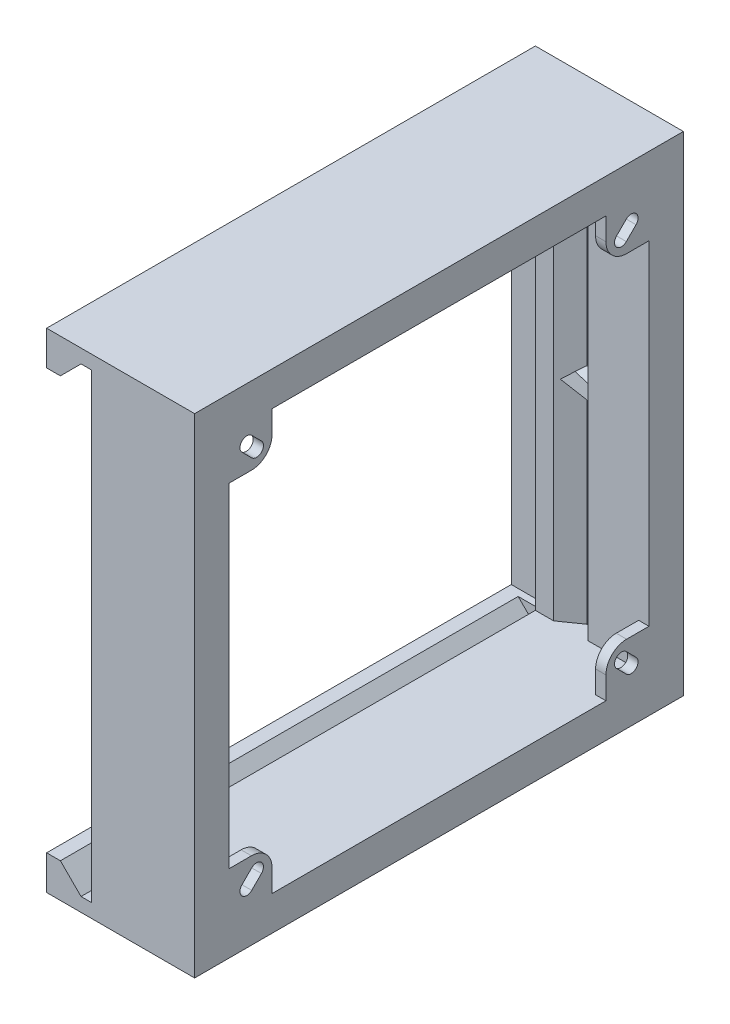
SolidWorks part; units mm, degrees
ref_plane "Front Plane" through (0, 0, 0) normal (1, 0, 0) x (0, 1, 0)
ref_plane "Top Plane" through (0, 0, 0) normal (0, 0, 1) x (0, 1, 0)
ref_plane "Right Plane" through (0, 0, 0) normal (0, 1, 0) x (-1, 0, 0)
sketch "Sketch2" plane through (0, 0, 0) normal (1, 0, 0) x (0, 1, 0)
  line L0 (-71, -71) -> (-71, 71)
  line L1 (-61, -61) -> (61, -61)
  line L2 (-61, -61) -> (-61, 61)
  line L3 (-61, 61) -> (61, 61)
  line L4 (61, -61) -> (61, 61)
  line L5 (-61, -61) -> (61, 61) construction
  line L6 (-61, 61) -> (61, -61) construction
  line L7 (-71, 71) -> (71, 71)
  line L8 (71, -71) -> (71, 71)
  line L9 (-71, -71) -> (71, -71)
  line L10 (-48.5, 61) -> (-48.5, 54.5)
  line L11 (-54.5, 48.5) -> (-61, 48.5)
  line L12 (-53, 53) -> (-55.8284, 55.8284) construction
  line L13 (-54.4142, 51.5858) -> (-57.2426, 54.4142)
  line L14 (-51.5858, 54.4142) -> (-54.4142, 57.2426)
  line L15 (48.5, 54.5) -> (48.5, 61)
  line L16 (61, 48.5) -> (54.5, 48.5)
  line L17 (53, 53) -> (55.8284, 55.8284) construction
  line L18 (51.5858, 54.4142) -> (54.4142, 57.2426)
  line L19 (54.4142, 51.5858) -> (57.2426, 54.4142)
  line L20 (54.5, -48.5) -> (61, -48.5)
  line L21 (48.5, -61) -> (48.5, -54.5)
  line L22 (53, -53) -> (55.8284, -55.8284) construction
  line L23 (54.4142, -51.5858) -> (57.2426, -54.4142)
  line L24 (51.5858, -54.4142) -> (54.4142, -57.2426)
  line L25 (-48.5, -54.5) -> (-48.5, -61)
  line L26 (-61, -48.5) -> (-54.5, -48.5)
  line L27 (-53, -53) -> (-55.8284, -55.8284) construction
  line L28 (-51.5858, -54.4142) -> (-54.4142, -57.2426)
  line L29 (-54.4142, -51.5858) -> (-57.2426, -54.4142)
  arc A0 (-48.5, 54.5) -> (-54.5, 48.5) centre (-54.5, 54.5) cw
  arc A2 (-54.4142, 51.5858) -> (-51.5858, 54.4142) centre (-53, 53) ccw
  arc A3 (-54.4142, 57.2426) -> (-57.2426, 54.4142) centre (-55.8284, 55.8284) ccw
  arc A4 (54.5, 48.5) -> (48.5, 54.5) centre (54.5, 54.5) cw
  arc A5 (51.5858, 54.4142) -> (54.4142, 51.5858) centre (53, 53) ccw
  arc A6 (57.2426, 54.4142) -> (54.4142, 57.2426) centre (55.8284, 55.8284) ccw
  arc A7 (48.5, -54.5) -> (54.5, -48.5) centre (54.5, -54.5) cw
  arc A8 (54.4142, -51.5858) -> (51.5858, -54.4142) centre (53, -53) ccw
  arc A9 (54.4142, -57.2426) -> (57.2426, -54.4142) centre (55.8284, -55.8284) ccw
  arc A10 (-54.5, -48.5) -> (-48.5, -54.5) centre (-54.5, -54.5) cw
  arc A11 (-51.5858, -54.4142) -> (-54.4142, -51.5858) centre (-53, -53) ccw
  arc A12 (-57.2426, -54.4142) -> (-54.4142, -57.2426) centre (-55.8284, -55.8284) ccw
  point P0 (0, 0)
  point P14 (-50.2574, 50.2574)
  point P18 (-54.4142, 54.4142)
  point P33 (54.4142, 54.4142)
  point P45 (54.4142, -54.4142)
  point P57 (-54.4142, -54.4142)
  point P62 (0, 0)
  dimension "D4" = 6
  dimension "D6" = 2
  dimension "D8" = 4
  dimension "D1" = 122
  dimension "D2" = 122
  dimension "D5" = 12.5
  dimension "D7" = 8
  dimension "D3" = 10
  dimension "D9" = 4
extrude "Boss-Extrude1" add sketch "Sketch2" along normal blind 3 contours A0 L10 L3 L2 L11 A3 L14 A2 L13 | L0 L9 L8 L7 L4 L1 L2 L3 | A4 L16 L4 L3 L15 A6 L19 A5 L18 | A7 L21 L1 L4 L20 A9 L24 A8 L23 | A10 L26 L2 L1 L25 A12 L29 A11 L28 region at (0, -68.9918, 0) region at (0, -60.8232, -54.75) region at (0, 48.6768, -57.75) region at (0, -60.8232, 54.75) region at (0, 57.75, 48.6768)
extrude "Boss-Extrude2" add sketch "Sketch2<4>" against normal blind 30 contours L0 L9 L8 L7 L4 L1 L2 L3 region at (0, -68.9918, 0)
sketch "Sketch2<4>" plane through (0, 0, 0) normal (1, 0, 0) x (0, 1, 0) same geometry as "Sketch2"
sketch "Sketch3" plane through (-30, 0, 0) normal (-1, 0, 0) x (0, -1, 0)
  line L0 (-61, -61) -> (-61, 61)
  line L1 (-61, 61) -> (-61, 71)
  line L2 (71, 71) -> (-71, 71) construction
  line L3 (-61, 71) -> (-71, 71)
  line L4 (71, -71) -> (71, 71)
  line L5 (71, 71) -> (-71, 71)
  line L6 (-71, 71) -> (-71, -71)
  line L7 (-71, -71) -> (71, -71)
  line L8 (71, -71) -> (71, 71)
  line L10 (-71, 71) -> (-71, -71)
  line L11 (-71, -71) -> (71, -71)
  line L12 (71, 71) -> (61, 71)
  line L13 (61, 71) -> (61, 61)
  line L14 (61, 61) -> (61, -61)
  line L15 (61, -61) -> (-61, -61)
  dimension "D1" = 0
extrude "Boss-Extrude3" add sketch "Sketch3" along normal blind 10
sketch "Sketch6" plane through (0, 0, -61) normal (0, 0, 1) x (1, 0, 0)
  line L0 (-30, 61) -> (-30, 67)
  line L1 (-30, 67) -> (-36, 61)
  line L2 (-36, 61) -> (-30, 61)
  line L6 (-40, 61) -> (0, 61) construction
  line L7 (-30, -61) -> (-30, 61) construction
  line L8 (55, 0) -> (-55, 0) construction
  line L9 (-30, -67) -> (-36, -61)
  line L10 (-30, -61) -> (-30, -67)
  line L11 (-36, -61) -> (-30, -61)
  dimension "D1" = 45
  dimension "D2" = 6
extrude "Cut-Extrude3" cut sketch "Sketch6" along normal up to surface (132 mm away) from offset 1 up to face at (-26.75, 0, 71) offset against normal yes
sketch "Sketch5" plane through (-40, 0, 0) normal (-1, 0, 0) x (0, -1, 0)
  line L0 (-61, -61) -> (61, -61)
  line L1 (61, -61) -> (61, -64)
  line L2 (61, -64) -> (-61, -64)
  line L3 (-61, -64) -> (-61, -61)
  dimension "D1" = 3
extrude "Cut-Extrude2" cut sketch "Sketch5" against normal up to surface (10 mm away) up to face at (-30, 0, -10.6)
sketch "Sketch9" plane through (0, -71, 0) normal (0, -1, 0) x (1, 0, 0)
  line L1 (3, 71) -> (-40, 71) construction
  line L3 (-30, 68) -> (-27, 71)
  line L4 (-30, 71) -> (-30, -62) construction
  line L5 (-27, 71) -> (-30, 71)
  line L6 (-30, 71) -> (-30, 68)
  dimension "D1" = 45
  dimension "D2" = 3
extrude "Cut-Extrude4" cut sketch "Sketch9" against normal up to vertex (138 mm away) and the other way up to vertex (-4 mm away) from surface up to point (-30, 67, 71) other way up to point (-30, -67, 71) starting at plane "Right Plane"
sketch "Sketch11" plane through (0, 71, 0) normal (0, 1, 0) x (-1, 0, 0)
  line L0 (14.7126, -65) -> (19, -65)
  line L1 (19, -65) -> (24.7126, -61)
  line L2 (24.7126, -61) -> (14.7126, -61)
  line L3 (14.7126, -61) -> (14.7126, -65)
  line L4 (-3, -71) -> (40, -71) construction
  line L5 (-3, -71) -> (-3, 71) construction
  point P2 (0, 0)
  point P9 (0, 0)
  point P10 (29.7902, -65)
  dimension "D1" = 10
  dimension "D2" = 4
  dimension "D3" = 35
  dimension "D4" = 6
  dimension "D5" = 22
extrude "Cut-Extrude5" cut sketch "Sketch11" against normal up to surface (132 mm away) and the other way up to surface (-10 mm away) from surface up to face at (-6.75, -61, 0) other way up to face at (-35.3333, 61, -18.3333) starting at plane "Right Plane"
sketch "Sketch13" plane through (-40, 0, 0) normal (-1, 0, 0) x (0, -1, 0)
  line L0 (0, -64) -> (0, -66) construction
  line L1 (-61, -64) -> (61, -64) construction
  line L2 (0, -66) -> (-5, -68.3553)
  line L3 (-5, -68.3553) -> (-2, -71)
  line L4 (-71, -71) -> (71, -71) construction
  line L5 (-2, -71) -> (2, -71)
  line L6 (2, -71) -> (5, -68.3553)
  line L7 (5, -68.3553) -> (0, -66)
  line L8 (-5, -68.3553) -> (5, -68.3553) construction
  point P5 (0, -71)
  point P12 (0, -68.3553)
  point P13 (-5, -69.0979)
  point P14 (-5, -68.3553)
  dimension "D1" = 10
  dimension "D2" = 2
  dimension "D3" = 4
extrude "Cut-Extrude6" cut sketch "Sketch13" against normal up to surface (25.2874 mm away) up to face at (-14.7126, 0, -63)
sketch "Sketch14" plane through (0, 0, -65) normal (0, 0, 1) x (1, 0, 0)
  line L0 (-18.5699, -5) -> (-14.7126, -5)
  line L2 (-14.7126, -5) -> (-14.7126, 5)
  line L3 (-18.033, 5) -> (-14.7126, 5)
  line L6 (-14.7126, -61) -> (-14.7126, 61) construction
  line L9 (3, -48.5) -> (3, 48.5) construction
  line L10 (-18.033, 5) -> (-23.5699, 0)
  line L11 (-23.5699, 0) -> (-18.5699, -5)
  point P1 (-16.3728, 0)
  point P7 (-16.4903, -1.5353)
  point P11 (3, 0)
  point P13 (0, 0)
  point P15 (-23.5306, 0)
  point P16 (-17.9938, 5.8824)
  point P17 (0, 0)
  point P19 (0, 0)
  point P20 (-14.7126, 0)
  line M5 (-14.7126, -61) -> (-14.7126, 61)
  line M7 (-19, 61) -> (-19, -61)
  dimension "D1" = 10
  dimension "D2" = 45
extrude "Cut-Extrude7" cut sketch "Sketch14" against normal up to vertex (3.3553 mm away) from surface contours L11 L0 L3 L10 M7 M5 | L10 L11 M7 region at (-16.8338, -0.0363, -65) region at (-20.5233, -0.1477, -65) up to point (-40, -5, -68.3553) starting at face at (-2.9281, 0, -61)
